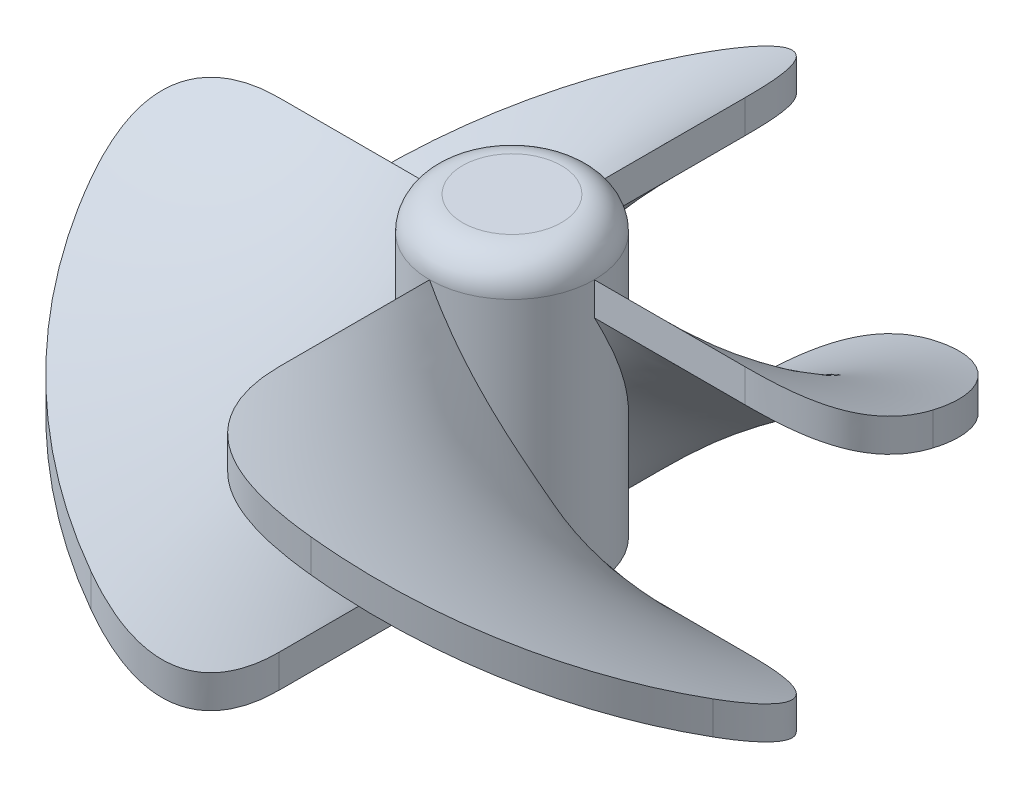
SolidWorks part; units mm, degrees
note: The reader was unsure of these and kept them because the rebuilt part matched: shared geometry of "Sketch1<2>".
ref_plane "Front Plane" through (0, 0, 0) normal (0, 0, 1) x (1, 0, 0)
ref_plane "Top Plane" through (0, 0, 0) normal (0, 1, 0) x (1, 0, 0)
ref_plane "Right Plane" through (0, 0, 0) normal (1, 0, 0) x (0, 0, -1)
sketch "Sketch1" plane through (0, 0, 0) normal (0, 1, 0) x (1, 0, 0)
  circle A0 centre (0, 0) radius 6.35
  dimension "D1" = 12.7
curve "Helix/Spiral1" pitch 76.2 height 19.05 radius 6.35 left hand yes centre (0, 0, 0) axis (0, 1, 0) start towards (0, 0, 1)
sketch "Sketch2" plane through (0, 0, 0) normal (0, 0, 1) x (1, 0, 0)
  line L0 (-6.35, 0) -> (0, 0) construction
  line L1 (-25.4, 1.27) -> (-6.35, 1.27)
  line L2 (-25.4, 1.27) -> (-25.4, -1.27)
  line L3 (-25.4, -1.27) -> (-6.35, -1.27)
  line L4 (-6.35, 1.27) -> (-6.35, -1.27)
  line L5 (-25.4, 1.27) -> (-6.35, -1.27) construction
  line L6 (-25.4, -1.27) -> (-6.35, 1.27) construction
  point P0 (-15.875, 0)
  dimension "D1" = 2.54
  dimension "D2" = 19.05
sweep "Sweep1" add profiles "Sketch2" path "Helix/Spiral1"
extrude "Boss-Extrude1" add sketch "Sketch1<2>" along normal blind 22.86 separate body
sketch "Sketch1<2>" plane through (0, 0, 0) normal (0, 1, 0) x (1, 0, 0) same geometry as "Sketch1"
fillet "Fillet2" radius 6.35 2 edges at (-25.4, 0, 0) conic rho 0.5
pattern_circular "CirPattern1" count 4 over 360 about axis through (0, 22.86, 0) along (0, -1, 0) of bodies 101
fillet "Fillet3" radius 2.54 1 edges at (0, 22.86, 6.35)
sketch "Sketch3" plane through (0, 0, 0) normal (0, -1, 0) x (1, 0, 0)
  circle A0 centre (0, 0) radius 1.016
  dimension "D1" = 2.032
extrude "Cut-Extrude1" cut sketch "Sketch3" against normal blind 20.32
